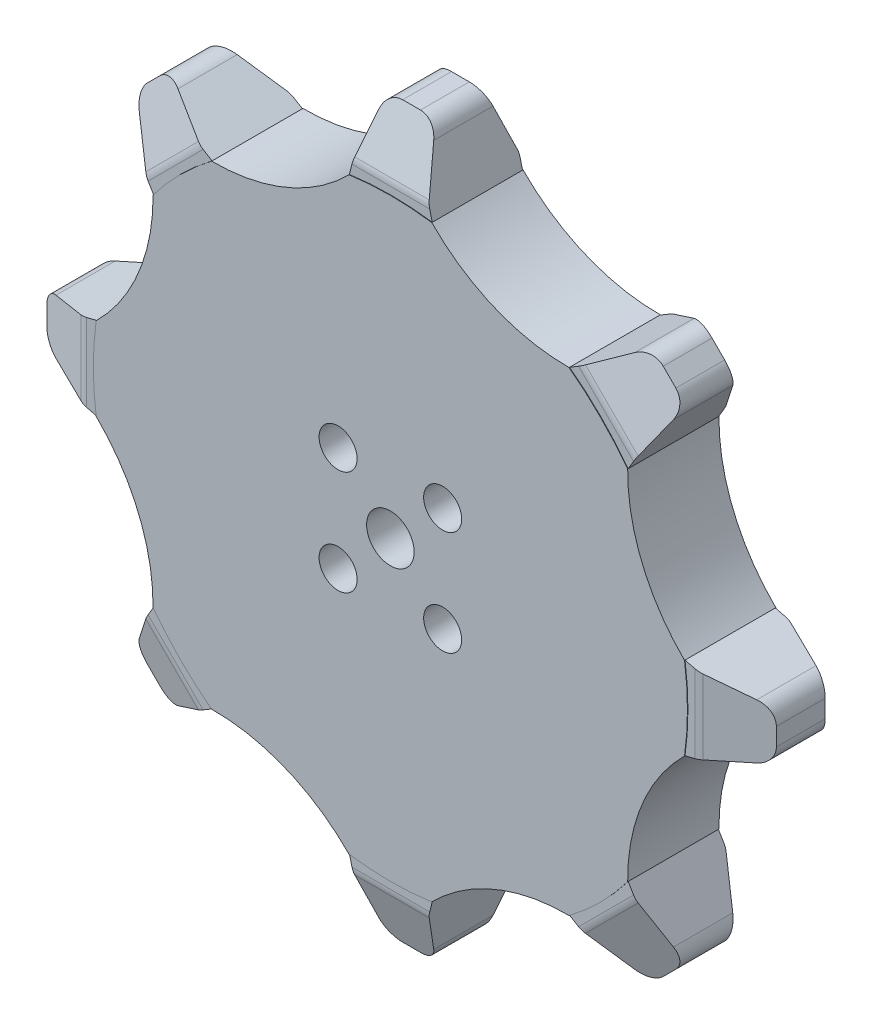
SolidWorks part; units mm, degrees
other "Markup1"
sketch "Sketch4" plane through (-30, 25, -15) normal (-0.7934, 0.0966, -0.601) x (-0.1502, -0.9879, 0.0395)
ref_plane "Front Plane" through (0, 0, 0) normal (0, 0, 1) x (1, 0, 0)
ref_plane "Top Plane" through (0, 0, 0) normal (0, 1, 0) x (1, 0, 0)
ref_plane "Right Plane" through (0, 0, 0) normal (1, 0, 0) x (0, 0, -1)
sketch "Sketch1" plane through (0, 0, 0) normal (0, 0, 1) x (1, 0, 0)
  line L0 (0, 0) -> (-50000, 0) construction
  circle A0 centre (0, 0) radius 31.25
  dimension "D1" = 62.5
extrude "Boss-Extrude1" add sketch "Sketch1" along normal mid plane 30
sketch "Sketch2" plane through (0, 0, 0) normal (0, 0, 1) x (1, 0, 0)
  line L0 (10.9478, 0) -> (-49989.0522, 0) construction
  line L1 (-28.3721, -5) -> (-28.3721, 5)
  line L2 (-28.3721, -5) -> (-38.3721, -2.5)
  line L3 (-28.3721, 5) -> (-38.3721, 2.5)
  line L4 (-38.3721, 2.5) -> (-38.3721, -2.5)
  line L5 (-33.6569, -15.7864) -> (-33.0873, 15.7864) construction
  point P6 (-28.3721, 0)
  point P13 (-33.3721, 0)
  dimension "D3" = 5
  dimension "D1" = 10
  dimension "D2" = 10
  dimension "D4" = 5
extrude "Boss-Extrude2" add sketch "Sketch2" along normal mid plane 9.5
sketch "Sketch8" plane through (0, 0, -15) normal (0, 0, -1) x (-1, 0, 0)
  line L0 (38.3721, 2.5) -> (38.3721, -2.5) construction
  line L1 (38.3721, 4.3667) -> (36.1221, 4.3667)
  line L2 (38.3721, 4.3667) -> (38.3721, -4.3553)
  line L3 (38.3721, -4.3553) -> (36.1221, -4.3553)
  line L4 (36.1221, 4.3667) -> (36.1221, -4.3553)
  dimension "D1" = 2.25
extrude "Cut-Extrude5" [suppressed] cut sketch "Sketch8" against normal blind 31
ref_plane "Plane2" through (0, 0, 0) normal (0, 1, 0) x (1, 0, 0)
chamfer "Chamfer1" distance 6 angle 20 1 edges at (-38.3721, 0, -4.75) first distance on face at (-34.7347, 0, -4.75)
chamfer "Chamfer2" distance 6 angle 20 1 edges at (-38.3721, 0, 4.75) first distance on face at (-34.7347, 0, 4.75)
fillet "Fillet11" radius 2 2 edges at (-38.3721, -2.5, 0) (-38.3721, 2.5, 0)
fillet "Fillet12" radius 2 2 edges at (-32.3721, 0, 4.75) (-32.3721, 0, -4.75)
pattern_circular "CirPattern1" count 8 over 360 about axis through (0, 0, 15) along (0, 0, -1) of "Boss-Extrude2", "Fillet11", "Chamfer1", "Chamfer2", "Fillet12"
sketch "Sketch3" plane through (0, 0, 15) normal (0, 0, 1) x (1, 0, 0)
  line L0 (5.5, 5.5) -> (-5.5, 5.5) construction
  line L5 (-5.5, 5.5) -> (5.5, -5.5) construction
  line L6 (-5.5, -5.5) -> (5.5, 5.5) construction
  line L7 (-5.5, 5.5) -> (-5.5, -5.5) construction
  line L8 (5.5, 5.5) -> (5.5, -5.5) construction
  line L9 (5.5, -5.5) -> (-5.5, -5.5) construction
  circle A0 centre (0, 0) radius 2.5
  circle A1 centre (5.5, 5.5) radius 2
  circle A2 centre (-5.5, 5.5) radius 2
  circle A3 centre (-5.5, -5.5) radius 2
  circle A4 centre (5.5, -5.5) radius 2
  dimension "D1" = 5
  dimension "D4" = 4
  dimension "D5" = 4
  dimension "D6" = 4
  dimension "D7" = 4
  dimension "D2" = 11
  dimension "D3" = 11
extrude "Cut-Extrude6" cut sketch "Sketch3" against normal through all
ref_point "Point1" [suppressed]
sketch "Sketch12" [suppressed] plane through (0, 0, -15) normal (0, 0, -1) x (-1, 0, 0)
  circle A0 centre (0, 0) radius 18.625
  dimension "D1" = 37.25
extrude "Cut-Extrude10" [suppressed] cut sketch "Sketch12" against normal blind 18
sketch "Sketch9" plane through (0, 0, -15) normal (0, 0, -1) x (-1, 0, 0)
  circle A0 centre (0, 0) radius 14.5
  dimension "D1" = 29
extrude "Cut-Extrude7" [suppressed] cut sketch "Sketch9" against normal offset from surface (10 mm away) 20 up to face at (7.5, -5.5, 15)
sketch "Sketch11" [suppressed] plane through (0, 0, -15) normal (0, 0, -1) x (-1, 0, 0)
  circle A0 centre (0, 0) radius 25
  circle A1 centre (0, 0) radius 14.5 construction
  circle A2 centre (0, 0) radius 14.5
  dimension "D1" = 50
extrude "Cut-Extrude9" [suppressed] cut sketch "Sketch11" against normal offset from surface (23 mm away) 7 up to face at (7.5, -5.5, 15)
fillet "Fillet9" [suppressed] radius 10
fillet "Fillet10" [suppressed] radius 2
sketch "Sketch13" [suppressed] plane through (0, 0, 3) normal (0, 0, -1) x (-1, 0, 0)
  circle A3 centre (0, 0) radius 15.125
  circle A4 centre (0, 0) radius 15.125
  circle A5 centre (0, 0) radius 18.625 construction
  circle A6 centre (0, 0) radius 18.625
  dimension "D1" = 3.5
extrude "Boss-Extrude3" [suppressed] add sketch "Sketch13" along normal offset from surface (11 mm away) 7 up to face at (7.5, -5.5, -15)
ref_plane "Plane3" through (0, 0, -4.8) normal (0, 0, -1) x (-1, 0, 0)
ref_plane "Plane4" through (0, 0, 4.8) normal (0, 0, 1) x (1, 0, 0)
sketch "Sketch14" plane through (0, 0, -4.8) normal (0, 0, -1) x (-1, 0, 0)
  line L1 (-46.4868, 40.1571) -> (68.2948, 40.1571)
  line L2 (-46.4868, 40.1571) -> (-46.4868, -59.8251)
  line L3 (-46.4868, -59.8251) -> (68.2948, -59.8251)
  line L4 (68.2948, 40.1571) -> (68.2948, -59.8251)
extrude "Cut-Extrude11" cut sketch "Sketch14" along normal blind 20
sketch "Sketch15" plane through (0, 0, 4.8) normal (0, 0, 1) x (1, 0, 0)
  line L1 (-95.8823, 60.4837) -> (98.5269, 60.4837)
  line L2 (-95.8823, 60.4837) -> (-95.8823, -68.9951)
  line L3 (-95.8823, -68.9951) -> (98.5269, -68.9951)
  line L4 (98.5269, 60.4837) -> (98.5269, -68.9951)
extrude "Cut-Extrude12" cut sketch "Sketch15" along normal blind 20
sketch "Sketch17" plane through (0, 0, 4.8) normal (0, 0, 1) x (1, 0, 0)
  line L0 (-3.9172, 32.7035) -> (-4.3568, 30.9448)
  line L1 (-20.355, 25.8947) -> (-18.8005, 24.962)
  line L2 (-20.355, 25.8947) -> (-3.9172, 32.7035)
  arc A0 (-18.8005, 24.962) -> (-4.3568, 30.9448) centre (-18.6236, 44.9612) ccw
extrude "Cut-Extrude13" cut sketch "Sketch17" against normal blind 20
pattern_circular "CirPattern3" count 8 over 360 about axis through (0, 0, 15) along (0, 0, -1) of "Cut-Extrude13"
